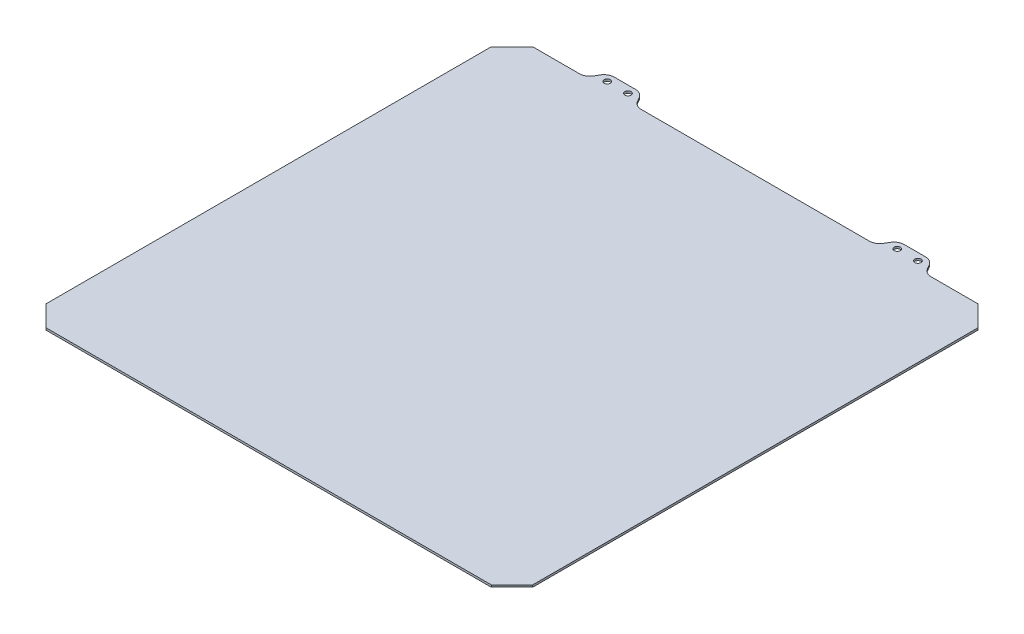
SolidWorks part; units mm, degrees
ref_plane "Front" through (0, 0, 0) normal (0, 0, 1) x (1, 0, 0)
ref_plane "Top" through (0, 0, 0) normal (0, 1, 0) x (1, 0, 0)
ref_plane "Right" through (0, 0, 0) normal (1, 0, 0) x (0, 0, -1)
sketch "Sketch1" plane through (0, 0, 0) normal (0, 1, 0) x (1, 0, 0)
  line L1 (117.5, 117.5) -> (-117.5, 117.5)
  line L2 (117.5, 117.5) -> (117.5, -117.5)
  line L3 (117.5, -117.5) -> (-117.5, -117.5)
  line L4 (-117.5, 117.5) -> (-117.5, -117.5)
  line L5 (0, -117.5) -> (0, 117.5) construction
  line L6 (117.5, 0) -> (-117.5, 0) construction
  point P0 (0, 0)
  dimension "D1" = 235
extrude "Boss-Extrude1" add sketch "Sketch1" along normal blind 1
sketch "Sketch2" plane through (0, 0, 0) normal (0, 1, 0) x (1, 0, 0)
  line L0 (-82.0415, 117.5) -> (-78, 124.5)
  line L1 (117.5, 117.5) -> (-117.5, 117.5) construction
  line L2 (-78, 124.5) -> (-62, 124.5)
  line L3 (-62, 124.5) -> (-57.9585, 117.5)
  line L4 (-57.9585, 117.5) -> (-82.0415, 117.5)
  line L5 (-70, 124.5) -> (-70, 117.5) construction
  line L6 (-75, 121) -> (-65, 121) construction
  line L7 (0, 0) -> (0, 117.5) construction
  line L8 (57.9585, 117.5) -> (82.0415, 117.5)
  line L9 (62, 124.5) -> (57.9585, 117.5)
  line L10 (75, 121) -> (65, 121) construction
  line L11 (70, 124.5) -> (70, 117.5) construction
  line L12 (78, 124.5) -> (62, 124.5)
  line L13 (82.0415, 117.5) -> (78, 124.5)
  circle A0 centre (-75, 121) radius 1.5
  circle A1 centre (-65, 121) radius 1.5
  circle A2 centre (65, 121) radius 1.5
  circle A3 centre (75, 121) radius 1.5
  point P12 (-70, 121)
  dimension "D2" = 3
  dimension "D1" = 10
  dimension "D3" = 60
  dimension "D4" = 7
  dimension "D5" = 16
  dimension "D6" = 130
extrude "Boss-Extrude2" add sketch "Sketch2" along normal blind 1
fillet "Fillet1" radius 5 8 edges at (-78, 0.5, -124.5) (-62, 0.5, -124.5) (-57.9585, 0.5, -117.5) (57.9585, 0.5, -117.5) (62, 0.5, -124.5) (78, 0.5, -124.5) (82.0415, 0.5, -117.5) (-82.0415, 0.5, -117.5)
chamfer "Chamfer1" distance 10 angle 45 4 edges at (117.5, 0.5, -117.5) (117.5, 0.5, 117.5) (-117.5, 0.5, 117.5) (-117.5, 0.5, -117.5)
